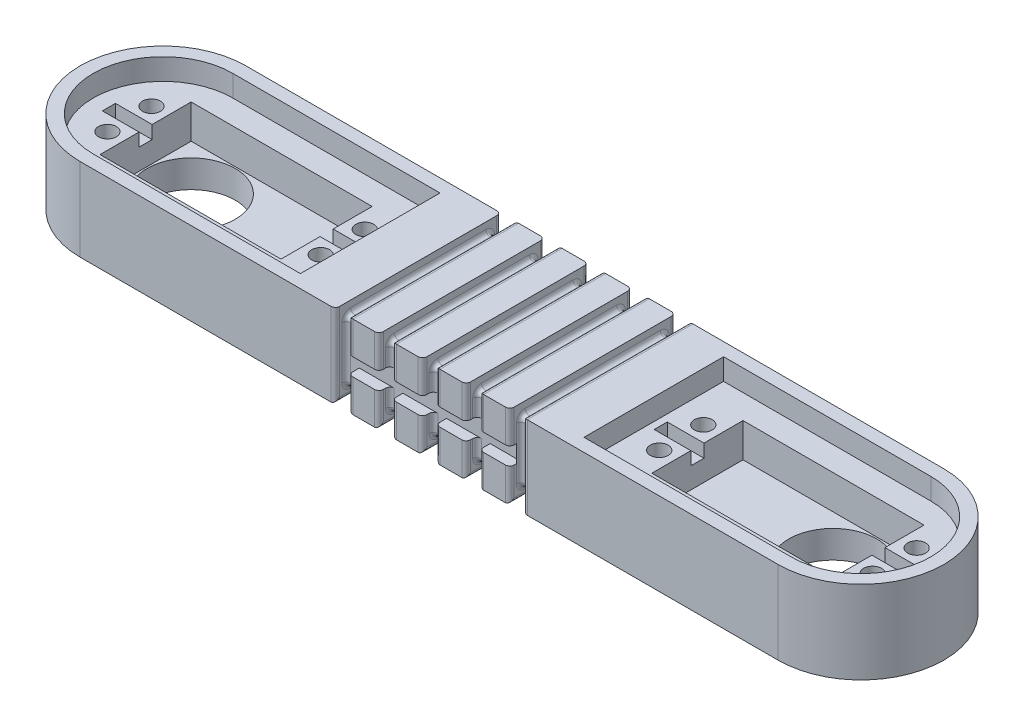
SolidWorks part; units mm, degrees
note: The reader was unsure of these and kept them because the rebuilt part matched: shared geometry of "草图2<3>", "草图2<4>".
ref_plane "前视基准面" through (0, 0, 0) normal (0, 0, 1) x (1, 0, 0)
ref_plane "上视基准面" through (0, 0, 0) normal (0, 1, 0) x (1, 0, 0)
ref_plane "右视基准面" through (0, 0, 0) normal (1, 0, 0) x (0, 0, -1)
sketch "草图1" plane through (0, 0, 0) normal (0, 1, 0) x (1, 0, 0)
  line L0 (-46.9393, 0) -> (46.9393, 0) construction
  line L1 (0, -46.9393) -> (0, 46.9393) construction
  line L2 (-80, 0) -> (80, 0) construction
  line L3 (-80, 19) -> (80, 19)
  line L4 (-80, -19) -> (80, -19)
  arc A0 (-80, 19) -> (-80, -19) centre (-80, 0) ccw
  arc A1 (80, -19) -> (80, 19) centre (80, 0) ccw
  point P7 (0, 0)
  dimension "D1" = 19
  dimension "D2" = 160
extrude "凸台-拉伸1" add sketch "草图1" along normal mid plane 19
sketch "草图2" plane through (0, 9.5, 0) normal (0, 1, 0) x (1, 0, 0)
  line L0 (-50, 0) -> (50, 0) construction
  line L1 (0, -50) -> (0, 50) construction
  line L2 (-80, 16) -> (-32.5, 16)
  line L3 (-80, -16) -> (-32.5, -16)
  line L4 (-32.5, 16) -> (-32.5, -16)
  line L5 (32.5, 16) -> (32.5, -16)
  line L6 (80, -16) -> (32.5, -16)
  line L7 (80, 16) -> (32.5, 16)
  line L8 (-63.25, 0) -> (-63.25, 10.45) construction
  line L9 (-84, -10.45) -> (-42.5, -10.45)
  line L10 (-84, -10.45) -> (-84, 10.45)
  line L11 (-84, 10.45) -> (-42.5, 10.45)
  line L12 (-42.5, -10.45) -> (-42.5, 10.45)
  line L13 (-84, -10.45) -> (-42.5, 10.45) construction
  line L14 (-84, 10.45) -> (-42.5, -10.45) construction
  line L15 (80, 19) -> (-80, 19) construction
  line L16 (-84, 10.45) -> (-73.55, 0) construction
  line L17 (84, 10.45) -> (73.55, 0) construction
  line L18 (84, 10.45) -> (42.5, -10.45) construction
  line L19 (84, -10.45) -> (42.5, 10.45) construction
  line L20 (63.25, 0) -> (63.25, 10.45) construction
  line L21 (42.5, -10.45) -> (42.5, 10.45)
  line L22 (84, 10.45) -> (42.5, 10.45)
  line L23 (84, -10.45) -> (84, 10.45)
  line L24 (84, -10.45) -> (42.5, -10.45)
  arc A0 (-80, 16) -> (-80, -16) centre (-80, 0) ccw
  arc A1 (-80, 19) -> (-80, -19) centre (-80, 0) ccw construction
  arc A2 (80, 16) -> (80, -16) centre (80, 0) cw
  circle A3 centre (-38.8, 5.05) radius 2.05
  circle A4 centre (-38.8, -5.05) radius 2.05
  circle A5 centre (-87.7, -5.05) radius 2.05
  circle A6 centre (-87.7, 5.05) radius 2.05
  circle A7 centre (-73.55, 0) radius 10.1
  circle A8 centre (73.55, 0) radius 10.1
  circle A9 centre (87.7, 5.05) radius 2.05
  circle A10 centre (87.7, -5.05) radius 2.05
  circle A11 centre (38.8, -5.05) radius 2.05
  circle A12 centre (38.8, 5.05) radius 2.05
  point P18 (-63.25, 0)
  point P55 (63.25, 0)
  dimension "D1" = 4.1
  dimension "D2" = 20.2
  dimension "D3" = 48.9
  dimension "D4" = 20.9
  dimension "D5" = 3
  dimension "D6" = 15
  dimension "D7" = 45
  dimension "D8" = 10.1
  dimension "D9" = 41.5
  dimension "D10" = 10
extrude "切除-拉伸1" cut sketch "草图2" against normal blind 4.9 contours L2 A0 L3 L4 A4 A3 L12 L9 L10 L11 A5 A6 | A2 L7 L5 L6 A10 A9 L23 L24 L21 L22 A11 A12
extrude "切除-拉伸2" cut sketch "草图2<3>" against normal blind 12.7 contours L9 L12 L11 L10 A7 | L24 L23 L22 L21 A8
sketch "草图2<3>" plane through (0, 9.5, 0) normal (0, 1, 0) x (1, 0, 0) same geometry as "草图2"
extrude "切除-拉伸3" cut sketch "草图2<4>" against normal through all contours A6 | A5 | A7 | A3 | A4 | A12 | A11 | A8 | A9 | A10
sketch "草图2<4>" plane through (0, 9.5, 0) normal (0, 1, 0) x (1, 0, 0) same geometry as "草图2"
sketch "草图3" plane through (0, -9.5, 0) normal (0, -1, 0) x (1, 0, 0)
  line L0 (-87.7, 5.05) -> (-73.55, 0) construction
  line L1 (-50, 0) -> (50, 0) construction
  line L2 (0, -50) -> (0, 50) construction
  line L3 (-85.0829, -1.9704) -> (-83.7244, -5.7767)
  line L4 (-83.7244, 5.7767) -> (-86.3416, 8.8563)
  line L5 (-86.3416, 8.8563) -> (-90.3171, 8.1296)
  line L6 (-90.3171, 8.1296) -> (-91.6756, 4.3233)
  line L7 (-91.6756, 4.3233) -> (-89.0584, 1.2437)
  line L8 (-89.0584, 1.2437) -> (-85.0829, 1.9704)
  line L9 (-85.0829, 1.9704) -> (-83.7244, 5.7767)
  line L10 (-89.0584, -1.2437) -> (-85.0829, -1.9704)
  line L11 (-91.6756, -4.3233) -> (-89.0584, -1.2437)
  line L12 (-90.3171, -8.1296) -> (-91.6756, -4.3233)
  line L13 (-86.3416, -8.8563) -> (-90.3171, -8.1296)
  line L14 (-83.7244, -5.7767) -> (-86.3416, -8.8563)
  line L15 (83.7244, -5.7767) -> (86.3416, -8.8563)
  line L16 (86.3416, -8.8563) -> (90.3171, -8.1296)
  line L17 (90.3171, -8.1296) -> (91.6756, -4.3233)
  line L18 (91.6756, -4.3233) -> (89.0584, -1.2437)
  line L19 (89.0584, -1.2437) -> (85.0829, -1.9704)
  line L20 (85.0829, 1.9704) -> (83.7244, 5.7767)
  line L21 (89.0584, 1.2437) -> (85.0829, 1.9704)
  line L22 (91.6756, 4.3233) -> (89.0584, 1.2437)
  line L23 (90.3171, 8.1296) -> (91.6756, 4.3233)
  line L24 (86.3416, 8.8563) -> (90.3171, 8.1296)
  line L25 (83.7244, 5.7767) -> (86.3416, 8.8563)
  line L26 (85.0829, -1.9704) -> (83.7244, -5.7767)
  line L27 (-34.7585, -5.05) -> (-36.7793, -8.55)
  line L28 (-36.7793, 8.55) -> (-40.8207, 8.55)
  line L29 (-40.8207, 8.55) -> (-42.8415, 5.05)
  line L30 (-42.8415, 5.05) -> (-40.8207, 1.55)
  line L31 (-40.8207, 1.55) -> (-36.7793, 1.55)
  line L32 (-36.7793, 1.55) -> (-34.7585, 5.05)
  line L33 (-34.7585, 5.05) -> (-36.7793, 8.55)
  line L34 (-36.7793, -1.55) -> (-34.7585, -5.05)
  line L35 (-40.8207, -1.55) -> (-36.7793, -1.55)
  line L36 (-42.8415, -5.05) -> (-40.8207, -1.55)
  line L37 (-40.8207, -8.55) -> (-42.8415, -5.05)
  line L38 (-36.7793, -8.55) -> (-40.8207, -8.55)
  line L39 (36.7793, -8.55) -> (40.8207, -8.55)
  line L40 (40.8207, -8.55) -> (42.8415, -5.05)
  line L41 (42.8415, -5.05) -> (40.8207, -1.55)
  line L42 (40.8207, -1.55) -> (36.7793, -1.55)
  line L43 (36.7793, -1.55) -> (34.7585, -5.05)
  line L44 (34.7585, 5.05) -> (36.7793, 8.55)
  line L45 (36.7793, 1.55) -> (34.7585, 5.05)
  line L46 (40.8207, 1.55) -> (36.7793, 1.55)
  line L47 (42.8415, 5.05) -> (40.8207, 1.55)
  line L48 (40.8207, 8.55) -> (42.8415, 5.05)
  line L49 (36.7793, 8.55) -> (40.8207, 8.55)
  line L50 (34.7585, -5.05) -> (36.7793, -8.55)
  circle A0 centre (-87.7, 5.05) radius 3.5 construction
  circle A1 centre (-87.7, -5.05) radius 3.5 construction
  circle A2 centre (87.7, -5.05) radius 3.5 construction
  circle A3 centre (87.7, 5.05) radius 3.5 construction
  circle A4 centre (-38.8, 5.05) radius 3.5 construction
  circle A5 centre (-38.8, -5.05) radius 3.5 construction
  circle A6 centre (38.8, -5.05) radius 3.5 construction
  circle A7 centre (38.8, 5.05) radius 3.5 construction
  dimension "D1" = 7
  dimension "D2" = 7
extrude "切除-拉伸4" cut sketch "草图3" against normal blind 3.2
sketch "草图4" plane through (0, 4.6, 0) normal (0, 1, 0) x (1, 0, 0)
  line L0 (-63.25, 10.45) -> (-63.25, 36.2041) construction
  line L1 (-84, 10.45) -> (-42.5, 10.45) construction
  line L2 (-50, 0) -> (50, 0) construction
  line L3 (0, -50) -> (0, 50) construction
  line L4 (-42.5, -10.45) -> (-42.5, 10.45) construction
  line L5 (-42.5, 1.5) -> (-34.1, 1.5)
  line L6 (-42.5, 1.5) -> (-42.5, -1.5)
  line L7 (-42.5, -1.5) -> (-34.1, -1.5)
  line L8 (-34.1, 1.5) -> (-34.1, -1.5)
  line L9 (-92.4, 1.5) -> (-92.4, -1.5)
  line L10 (-84, -1.5) -> (-92.4, -1.5)
  line L11 (-84, 1.5) -> (-84, -1.5)
  line L12 (-84, 1.5) -> (-92.4, 1.5)
  line L13 (84, 1.5) -> (92.4, 1.5)
  line L14 (84, 1.5) -> (84, -1.5)
  line L15 (84, -1.5) -> (92.4, -1.5)
  line L16 (92.4, 1.5) -> (92.4, -1.5)
  line L17 (34.1, 1.5) -> (34.1, -1.5)
  line L18 (42.5, -1.5) -> (34.1, -1.5)
  line L19 (42.5, 1.5) -> (42.5, -1.5)
  line L20 (42.5, 1.5) -> (34.1, 1.5)
  dimension "D1" = 3
  dimension "D2" = 8.4
extrude "切除-拉伸5" cut sketch "草图4" against normal blind 3
sketch "草图5" plane through (0, 0, 0) normal (1, 0, 0) x (0, 0, -1)
  line L0 (-16.5, 7) -> (16.5, 7)
  line L1 (-19, 9.5) -> (19, 9.5)
  line L2 (-19, 9.5) -> (-19, -9.5)
  line L3 (-19, -9.5) -> (19, -9.5)
  line L4 (19, 9.5) -> (19, -9.5)
  line L5 (16.5, 7) -> (16.5, -7)
  line L6 (-16.5, -7) -> (16.5, -7)
  line L7 (-16.5, 7) -> (-16.5, -7)
  dimension "D1" = 2.5
extrude "切除-拉伸6" cut sketch "草图5" against normal mid plane 3
fillet "圆角1" radius 1 15 edges at (1.5, 0, -19) (-1.5, 0, -19) (1.5, -9.5, 0) (-1.5, -9.5, 0) (1.5, 0, 19) (1.5, 9.5, 0) (-1.5, 0, 19) (-1.5, 7, 0) (-1.5, -7, 0) (-1.5, 0, -16.5) (-1.5, 0, 16.5) (0, 7, -16.5) (0, 7, 16.5) (0, -7, 16.5) (0, -7, -16.5)
pattern_linear "阵列(线性)1" count 3 spacing 10 along (-1, 0, 0) count 3 spacing 10 along (1, 0, 0) of "切除-拉伸6", "圆角1"
sketch "草图6" plane through (0, 0, -19) normal (0, 0, -1) x (-1, 0, 0)
  line L0 (18.5, -6) -> (18.5, 6) construction
  line L1 (-18.5, -2) -> (18.5, -2)
  line L2 (-18.5, -2) -> (-18.5, 2)
  line L3 (-18.5, 2) -> (18.5, 2)
  line L4 (18.5, -2) -> (18.5, 2)
  line L5 (-18.5, -2) -> (18.5, 2) construction
  line L6 (-18.5, 2) -> (18.5, -2) construction
  point P0 (0, 0)
  dimension "D1" = 4
extrude "切除-拉伸7" cut sketch "草图6" against normal blind 2.5
mirror "镜向2" about plane through (0, 0, 0) normal (0, 0, 1) of "切除-拉伸7"
